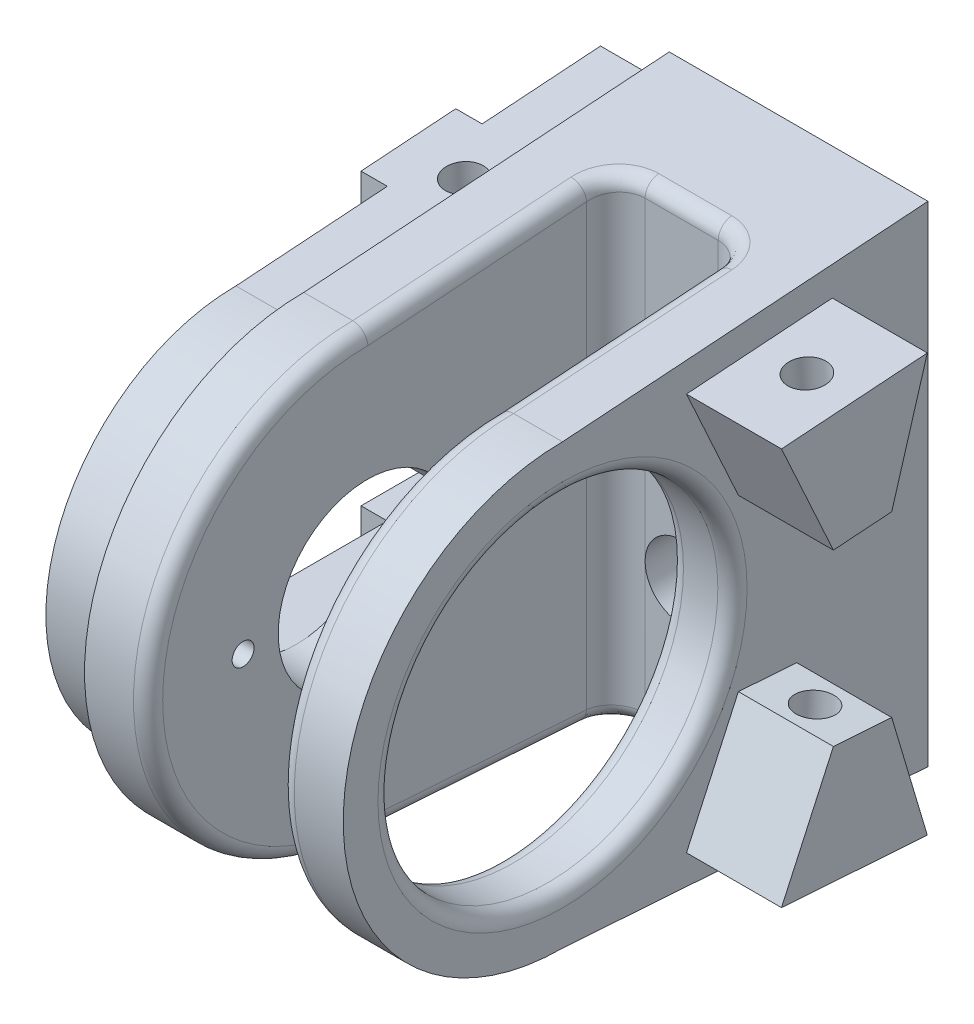
SolidWorks part; units mm, degrees
ref_plane "Front Plane" through (0, 0, 0) normal (0, 0, 1) x (1, 0, 0)
ref_plane "Top Plane" through (0, 0, 0) normal (0, 1, 0) x (1, 0, 0)
ref_plane "Right Plane" through (0, 0, 0) normal (1, 0, 0) x (0, 0, -1)
sketch "Sketch7" plane through (0, 0, 0) normal (1, 0, 0) x (0, 0, -1)
  line L2 (0, -15) -> (25, -16.7482)
  line L3 (0, 15) -> (25, 16.7482)
  line L5 (25, 16.7482) -> (25, -16.7482)
  arc A0 (0, 15) -> (0, -15) centre (0, 0) ccw
  dimension "D1" = 15
  dimension "D2" = 25
extrude "Boss-Extrude2" add sketch "Sketch7" along normal mid plane 27.1
sketch "Sketch8" plane through (-13.55, 0, 0) normal (-1, 0, 0) x (0, 0, 1)
  line L0 (-16.9, -6.1) -> (6.1, -6.1)
  line L2 (6.1, -6.1) -> (6.1, 6.1)
  line L3 (6.1, 6.1) -> (-16.9, 6.1)
  line L4 (-16.9, 6.1) -> (-16.9, -6.1)
  dimension "D1" = 23
  dimension "D2" = 12.2
  dimension "D3" = 6.1
  dimension "D4" = 6.1
extrude "Cut-Extrude6" cut sketch "Sketch8" against normal blind 4.2
sketch "Sketch9" plane through (-9.35, 0, 0) normal (-1, 0, 0) x (0, 0, 1)
  line L0 (-6.1, 0) -> (-5.95, 0)
  line L1 (6.1, -6.1) -> (6.1, 6.1) construction
  arc A0 (-5.3706, -2.8925) -> (-5.3706, 2.8925) centre (0, 0) ccw
  arc A1 (-5.3706, 2.8925) -> (-5.3706, -2.8925) centre (-5.95, 0) ccw
  point P8 (-8.9, 0)
  dimension "D1" = 2.95
  dimension "D2" = 15
extrude "Cut-Extrude7" cut sketch "Sketch9" against normal through all contours A0 A1 region at (-9.35, 0, -0.7745)
sketch "Sketch10" plane through (0, 0, 0) normal (1, 0, 0) x (0, 0, -1)
  line L0 (-15, -16.7482) -> (-15, 16.7482)
  line L1 (17, -16.7482) -> (-15, -16.7482)
  line L2 (17, 16.7482) -> (17, -16.7482)
  line L3 (-15, 16.7482) -> (17, 16.7482)
extrude "Cut-Extrude8" cut sketch "Sketch10" against normal mid plane 9
sketch "Sketch11" plane through (13.55, 0, 0) normal (1, 0, 0) x (0, 0, -1)
  circle A0 centre (0, 0) radius 11.625
extrude "Cut-Extrude9" cut sketch "Sketch11" against normal up to next
sketch "Sketch12" plane through (13.55, 0, 0) normal (1, 0, 0) x (0, 0, -1)
  line L0 (25, 16.7482) -> (25, -16.7482)
  line L1 (25, -16.7482) -> (0, -15)
  line L2 (25, 16.7482) -> (0, 15)
  arc A0 (0, 15) -> (0, -15) centre (0, 0) ccw
extrude "Cut-Extrude10" cut sketch "Sketch12" against normal blind 4.7
fillet "Fillet2" radius 1 2 edges at (8.85, 0, -11.625) (4.5, 0, 11.625)
fillet "Fillet3" radius 2 2 edges at (4.5, 0, -17) (-4.5, 0, -17)
sketch "Sketch13" plane through (0, 0, -17) normal (0, 0, 1) x (1, 0, 0)
  circle A0 centre (0, 0) radius 0.75
  circle A1 centre (0, -6.25) radius 2.5
  circle A2 centre (0, -13.5) radius 0.75
extrude "Cut-Extrude11" cut sketch "Sketch13" against normal up to next
sketch "Sketch14" plane through (-13.55, 0, 0) normal (-1, 0, 0) x (0, 0, 1)
  line L0 (-25, 14.7482) -> (-25, 16.7482)
  line L1 (-25, -16.7482) -> (-25, 16.7482) construction
  line L2 (-25, 14.7482) -> (-0.0609, 13.0043)
  line L3 (-25, -14.7482) -> (-0.0609, -13.0043)
  line L4 (-25, 16.7482) -> (0, 15)
  line L5 (-25, -16.7482) -> (0, -15)
  line L6 (-25, -16.7482) -> (-25, -14.7482)
  arc A0 (-0.0609, 13.0043) -> (-0.0609, -13.0043) centre (-0.0609, 0) cw
  arc A1 (0, 15) -> (0, -15) centre (0, 0) cw
extrude "Cut-Extrude12" cut sketch "Sketch14" against normal blind 4.7
sketch "Sketch15" plane through (8.85, 0, 0) normal (1, 0, 0) x (0, 0, -1)
  line L2 (18.4558, -14.2857) -> (19.0139, -6.3052)
  line L3 (18.4558, 14.2857) -> (8.4802, 13.5881)
  line L4 (8.4802, 13.5881) -> (9.0382, 5.6076)
  line L5 (9.0382, 5.6076) -> (19.0139, 6.3052)
  line L6 (18.4558, 14.2857) -> (19.0139, 6.3052)
  line L7 (9.0382, -5.6076) -> (19.0139, -6.3052)
  line L8 (8.4802, -13.5881) -> (9.0382, -5.6076)
  line L9 (18.4558, -14.2857) -> (8.4802, -13.5881)
extrude "Boss-Extrude3" add sketch "Sketch15" along normal blind 6.5
sketch "Sketch17" plane through (0, 12.9319, 0.9043) normal (0, 0.9976, 0.0698) x (1, 0, 0)
  circle A0 centre (12.1, 14.4074) radius 1.3
extrude "Cut-Extrude13" cut sketch "Sketch17" against normal blind 8
sketch "Sketch18" plane through (0, 12.9367, 0.9046) normal (0, 0.9976, 0.0698) x (1, 0, 0)
  circle A0 centre (-11.2, 14.2679) radius 1.3
extrude "Cut-Extrude14" cut sketch "Sketch18" against normal blind 8
mirror "Mirror1" about plane through (0, 0, 0) normal (0, 1, 0) of "Cut-Extrude14"
sketch "Sketch19" plane through (0, -4.9514, 0.3462) normal (0, 0.9976, -0.0698) x (1, 0, 0)
  circle A0 centre (12.1, 14.4074) radius 1.3
extrude "Cut-Extrude15" cut sketch "Sketch19" against normal blind 8
fillet "Fillet5" radius 1 12 edges at (4.5, -15.5245, -7.5) (3.9142, -16.1478, -16.4142) (-4.5, -15.5245, -7.5) (-3.9142, -16.1478, -16.4142) (-4.5, 15.5245, -7.5) (-3.9142, 16.1478, -16.4142) (4.5, 15.5245, -7.5) (3.9142, 16.1478, -16.4142) (0, -16.1888, -17) (4.5, 0, 15) (-4.5, 0, 15) (0, 16.1888, -17)
sketch "Sketch20" plane through (-13.55, 0, 0) normal (-1, 0, 0) x (0, 0, 1)
  circle A0 centre (-19.3, 0) radius 0.75
  circle A1 centre (8.5, 0) radius 0.75
extrude "Cut-Extrude16" cut sketch "Sketch20" against normal blind 10
sketch "Sketch23" plane through (15.35, 0, 0) normal (1, 0, 0) x (0, 0, -1)
  line L0 (9.0382, 5.6076) -> (12.0309, 5.8169)
  line L1 (11.2339, 5.7611) -> (19.0139, 6.3052) construction
  line L2 (12.0309, 5.8169) -> (8.4802, 13.5881)
  line L3 (8.4802, 13.5881) -> (9.0382, 5.6076)
  line L4 (19.0139, 6.3052) -> (16.0212, 6.0959)
  line L5 (16.0212, 6.0959) -> (18.4558, 14.2857)
  line L6 (18.4558, 14.2857) -> (19.0139, 6.3052)
extrude "Cut-Extrude18" cut sketch "Sketch23" against normal up to surface (6.5 mm away) up to face at (8.85, 0, -8.75)
sketch "Sketch24" plane through (15.35, 0, 0) normal (1, 0, 0) x (0, 0, -1)
  line L0 (9.0382, -5.6076) -> (12.0309, -5.8169)
  line L1 (19.0139, -6.3052) -> (11.2339, -5.7611) construction
  line L2 (12.0309, -5.8169) -> (8.4802, -13.5881)
  line L3 (19.0139, -6.3052) -> (16.0212, -6.0959)
  line L4 (19.0139, -6.3052) -> (9.0382, -5.6076) construction
  line L5 (16.0212, -6.0959) -> (18.4558, -14.2857)
  line L6 (18.4558, -14.2857) -> (19.0139, -6.3052)
  line L7 (8.4802, -13.5881) -> (9.0382, -5.6076)
extrude "Cut-Extrude19" cut sketch "Sketch24" against normal up to surface (6.5 mm away) up to face at (8.85, 9.9466, -13.747)
sketch "Sketch25" plane through (-13.55, 0, 0) normal (-1, 0, 0) x (0, 0, 1)
  line L0 (-16.9, 6.1) -> (-16.9, 14.1818)
  line L1 (-25, 14.7482) -> (-0.0609, 13.0043) construction
  line L2 (-16.9, 14.1818) -> (-10.4158, 13.7283)
  line L3 (-25, 14.7482) -> (-0.0609, 13.0043) construction
  line L4 (-10.4158, 13.7283) -> (-10.4158, 6.1)
  line L5 (0, 6.1) -> (-16.9, 6.1) construction
  line L6 (-10.4158, 6.1) -> (-16.9, 6.1)
  line L9 (-10.4158, -13.7283) -> (-10.4158, -6.1)
  line L10 (-10.4158, -6.1) -> (-16.9, -6.1)
  line L11 (-16.9, -6.1) -> (-16.9, -14.1818)
  line L12 (-16.9, -14.1818) -> (-10.4158, -13.7283)
extrude "Boss-Extrude4" add sketch "Sketch25" along normal blind 1.8
